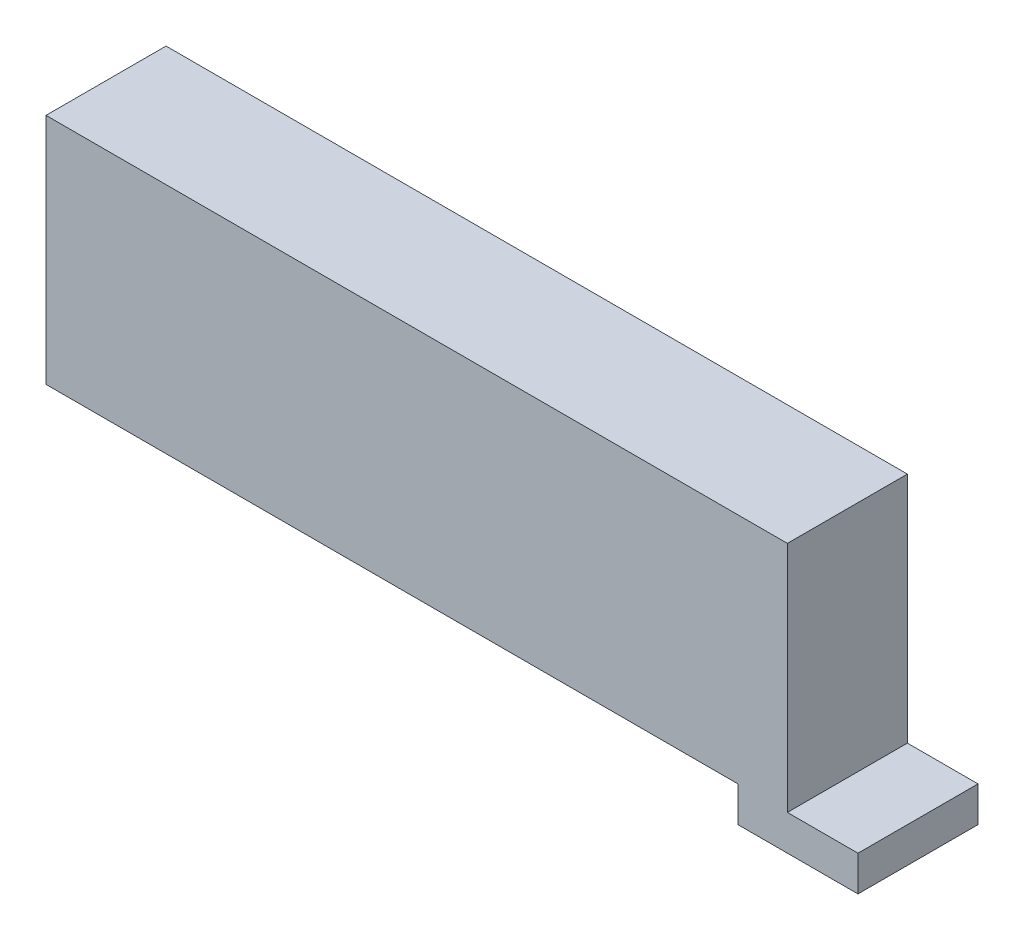
SolidWorks part; units mm, degrees
ref_plane "Front Plane" through (0, 0, 0) normal (0, 0, 1) x (1, 0, 0)
ref_plane "Top Plane" through (0, 0, 0) normal (0, 1, 0) x (1, 0, 0)
ref_plane "Right Plane" through (0, 0, 0) normal (1, 0, 0) x (0, 0, -1)
sketch "Sketch1" plane through (0, 0, 0) normal (0, 0, 1) x (1, 0, 0)
  line L1 (-52.5, -16.5) -> (52.5, -16.5)
  line L2 (-52.5, -16.5) -> (-52.5, 16.5)
  line L3 (-52.5, 16.5) -> (52.5, 16.5)
  line L4 (52.5, -16.5) -> (52.5, 16.5)
  line L5 (-52.5, -16.5) -> (52.5, 16.5) construction
  line L6 (-52.5, 16.5) -> (52.5, -16.5) construction
  point P0 (0, 0)
  dimension "D1" = 105
  dimension "D2" = 33
extrude "Boss-Extrude1" add sketch "Sketch1" along normal blind 17
sketch "Sketch2" plane through (0, -16.5, 0) normal (0, -1, 0) x (1, 0, 0)
  line L0 (-52.5, 0) -> (52.5, 0) construction
  line L1 (52.5, 17) -> (45.5, 17)
  line L2 (52.5, 17) -> (52.5, 0)
  line L3 (52.5, 0) -> (45.5, 0)
  line L4 (45.5, 17) -> (45.5, 0)
  dimension "D1" = 7
extrude "Boss-Extrude2" add sketch "Sketch2" along normal blind 5
sketch "Sketch3" plane through (52.5, 0, 0) normal (1, 0, 0) x (0, 0, -1)
  line L0 (0, -21.5) -> (0, 16.5) construction
  line L1 (-17, -21.5) -> (0, -21.5)
  line L2 (-17, -21.5) -> (-17, -16.5)
  line L3 (-17, -16.5) -> (0, -16.5)
  line L4 (0, -21.5) -> (0, -16.5)
  dimension "D1" = 5
extrude "Boss-Extrude3" add sketch "Sketch3" along normal blind 10
